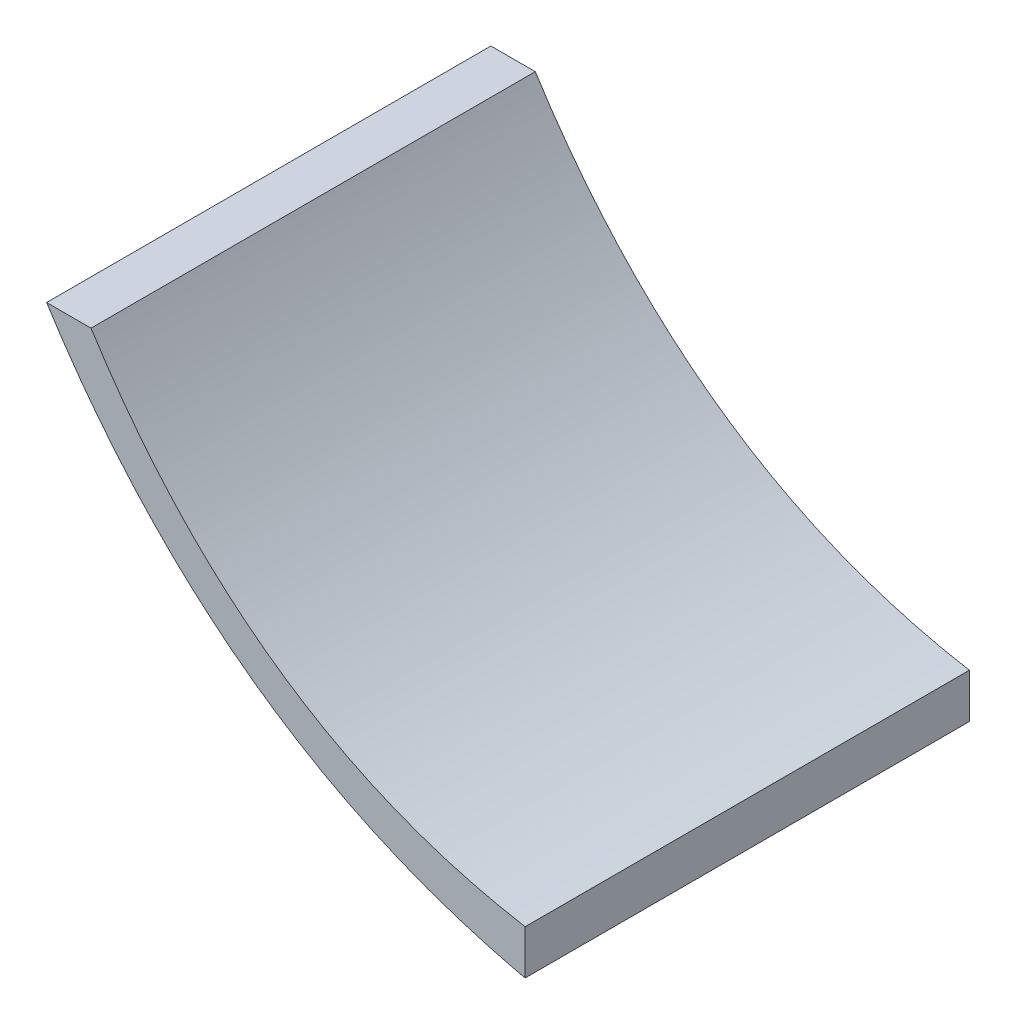
SolidWorks part; units mm, degrees
material "ALUMINUM 6061-T6"
ref_plane "Front Plane" through (0, 0, 0) normal (0, 0, 1) x (1, 0, 0)
ref_plane "Top Plane" through (0, 0, 0) normal (0, 1, 0) x (1, 0, 0)
ref_plane "Right Plane" through (0, 0, 0) normal (1, 0, 0) x (0, 0, -1)
sketch "Sketch1" plane through (0, 0, 0) normal (0, 0, 1) x (1, 0, 0)
  line L0 (-124.1009, 83.4447) -> (-136.8009, 83.4447)
  line L1 (0, -15.3818) -> (0, -2.6818)
  spline S0 degree 2 poles (-124.1009, 83.4447) (-77.9925, 10.6612) (0, -2.6818) knots 0 0 0 1 1 1
  spline S1 degree 2 poles (-136.8009, 83.4447) (-86.4912, 4.1154) (0, -15.3818) knots 0 0 0 1 1 1
  point P5 (0, 0)
extrude "Boss-Extrude1" add sketch "Sketch1" along normal mid plane 127 contours S0 L1 S1 L0
